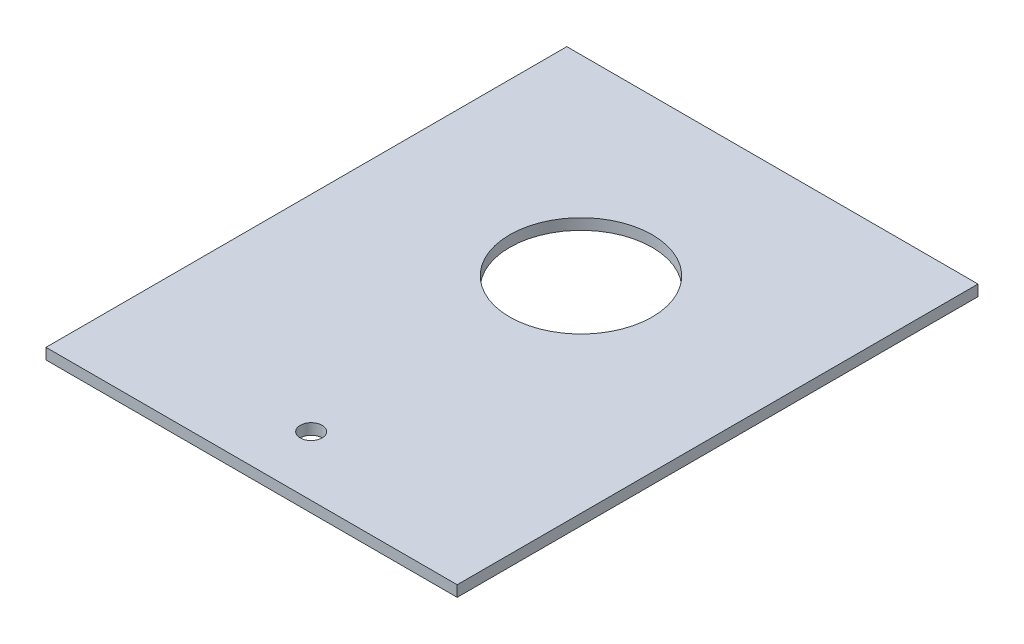
SolidWorks part; units mm, degrees
ref_plane "Front Plane" through (0, 0, 0) normal (0, 0, 1) x (1, 0, 0)
ref_plane "Top Plane" through (0, 0, 0) normal (0, 1, 0) x (1, 0, 0)
ref_plane "Right Plane" through (0, 0, 0) normal (1, 0, 0) x (0, 0, -1)
sketch "Sketch1" plane through (0, 0, 0) normal (0, 1, 0) x (1, 0, 0)
  line L0 (75, 69.8429) -> (75, -120.1571) construction
  line L1 (-75, -120.1571) -> (75, -120.1571) construction
  line L2 (-75, 69.8429) -> (75, 69.8429) construction
  line L3 (-75, 69.8429) -> (-75, -120.1571) construction
  line L4 (75, 69.8429) -> (75, -120.1571)
  line L5 (-75, -120.1571) -> (75, -120.1571)
  line L6 (-75, 69.8429) -> (75, 69.8429)
  line L7 (-75, 69.8429) -> (-75, -120.1571)
extrude "Boss-Extrude1" add sketch "Sketch1" against normal blind 4
hole_wizard "Hole1" positions "Sketch2" profile "Sketch3" legacy
sketch "Sketch2" plane through (0, 0, 0) normal (0, 1, 0) x (1, 0, 0)
  point P0 (0, 0)
sketch "Sketch3" plane through (0, 0, 0) normal (1, 0, 0) x (0, 0, 1)
  line L0 (0, 0) -> (0, 10)
  line L1 (0, 10) -> (26, 10)
  line L2 (26, 10) -> (26, 0)
  line L3 (26, 0) -> (0, 0)
  line L4 (0, 110) -> (0, -10) construction
  dimension "Diameter" = 52
  dimension "Depth" = 10
hole_wizard "Hole2" positions "Sketch4" profile "Sketch5" legacy
sketch "Sketch4" plane through (0, 0, 0) normal (0, 1, 0) x (1, 0, 0)
  point P0 (0, -98.42)
sketch "Sketch5" plane through (0, 0, 98.42) normal (1, 0, 0) x (0, 0, 1)
  line L0 (0, 0) -> (0, 100)
  line L1 (0, 100) -> (4, 100)
  line L2 (4, 100) -> (4, 0)
  line L3 (4, 0) -> (0, 0)
  line L4 (0, 110) -> (0, -10) construction
  dimension "Diameter" = 8
  dimension "Depth" = 100
